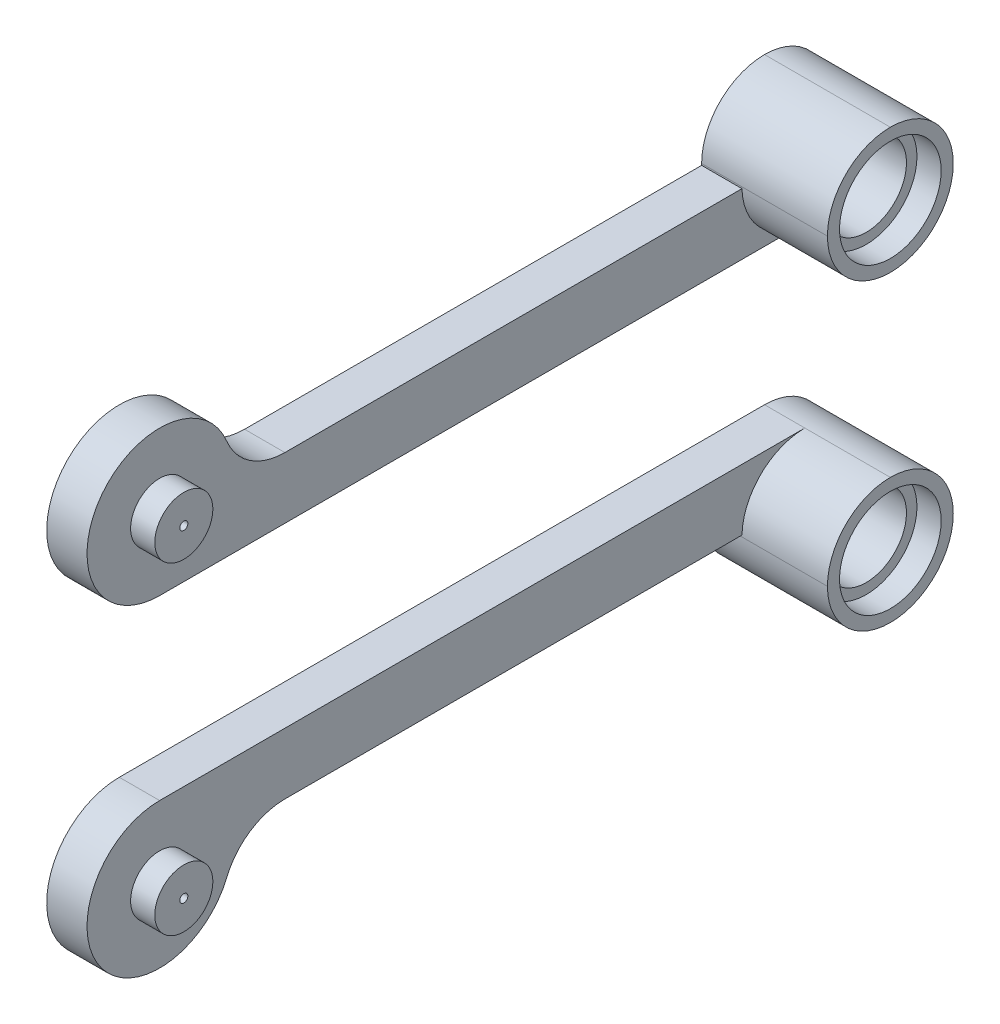
SolidWorks part; units mm, degrees
ref_plane "前视基准面" through (0, 0, 0) normal (0, 0, 1) x (1, 0, 0)
ref_plane "上视基准面" through (0, 0, 0) normal (0, 1, 0) x (1, 0, 0)
ref_plane "右视基准面" through (0, 0, 0) normal (1, 0, 0) x (0, 0, -1)
other "Configuration Table"
sketch "草图1" plane through (0, 0, 0) normal (1, 0, 0) x (0, 0, -1)
  line L0 (40, 3.3) -> (40, -4.5) construction
  line L1 (0, -4.5) -> (43.9, -4.5)
  line L2 (0, -4.5) -> (0, 3.3)
  line L3 (0, 3.3) -> (43.9, 3.3)
  line L4 (43.9, -4.5) -> (43.9, 3.3)
  line L6 (36.1, -4.5) -> (43.9, -4.5)
  line L7 (36.1, -4.5) -> (36.1, 3.3)
  line L8 (36.1, 3.3) -> (43.9, 3.3)
  line L9 (43.9, -4.5) -> (43.9, 3.3)
  line L10 (36.1, -4.5) -> (43.9, 3.3) construction
  line L11 (36.1, 3.3) -> (43.9, -4.5) construction
  circle A4 centre (0, 0) radius 1.8
  circle A5 centre (0, 0) radius 4.5
  circle A6 centre (40, -0.6) radius 2.5
  circle A7 centre (40, -0.6) radius 3.15
  circle A8 centre (0, 0) radius 0.25
  point P9 (40, -0.6)
  dimension "D1" = 3.6
  dimension "D4" = 40
  dimension "D5" = 3.9
  dimension "D2" = 9
  dimension "D6" = 5
  dimension "D7" = 6.3
  dimension "D8" = 0.5
  dimension "D3" = 7.8
extrude "凸台-拉伸1" add sketch "草图1" along normal blind 2.5 contours A5 | L3 L4 L1 L2
extrude "凸台-拉伸3" add sketch "草图1<6>" along normal blind 1.5 from surface contours L2 A4 | L2 A4 region at (0, 0, 0.7769) region at (0, 0, -0.7769) starting at face at (2.5, -0.0392, -21.2851)
sketch "草图1<6>" plane through (0, 0, 0) normal (1, 0, 0) x (0, 0, -1) same geometry as "草图1"
extrude "凸台-拉伸2" add sketch "草图1<5>" along normal blind 7.8 contours A6 | A7 A6 | L7 L1 L4 L3 A7 region at (0, -0.6, -36.2103) region at (0, -0.6, -40) region at (0, -0.6, -36.9391)
sketch "草图1<5>" plane through (0, 0, 0) normal (1, 0, 0) x (0, 0, -1) same geometry as "草图1"
extrude "切除-拉伸1" cut sketch "草图1<7>" along normal through all contours A6 region at (0, -0.6, -40)
sketch "草图1<7>" plane through (0, 0, 0) normal (1, 0, 0) x (0, 0, -1) same geometry as "草图1"
extrude "切除-拉伸2" cut sketch "草图1<8>" along normal blind 1.5 contours A7 A6 region at (0, -0.6, -36.9391)
sketch "草图1<8>" plane through (0, 0, 0) normal (1, 0, 0) x (0, 0, -1) same geometry as "草图1"
extrude "切除-拉伸3" cut sketch "草图1<9>" against normal blind 1.5 from surface contours A7 A6 region at (0, -0.6, -36.9391) starting at face at (7.8, -0.6, -42.5)
sketch "草图1<9>" plane through (0, 0, 0) normal (1, 0, 0) x (0, 0, -1) same geometry as "草图1"
sketch "草图2" plane through (0, 0, 0) normal (-1, 0, 0) x (0, 0, 1)
  line L0 (-3.0594, 3.3) -> (-43.9, 3.3) construction
  line L1 (-36.1, 3.3) -> (-4.5, 3.3)
  line L2 (-36.1, 3.3) -> (-36.1, -0.7)
  line L3 (-36.1, -0.7) -> (-4.5, -0.7)
  line L4 (-4.5, 3.3) -> (-4.5, -0.7)
  line L5 (-36.1, 3.3) -> (-36.1, -4.5) construction
  line L6 (-4.5, 3.3) -> (-3.0594, 3.3)
  arc A1 (0, -4.5) -> (-3.0594, 3.3) centre (0, 0) ccw construction
  circle A2 centre (0, 0) radius 4.5
  line M7 (-3.0594, 3.3) -> (-43.9, 3.3)
  dimension "D1" = 4
extrude "切除-拉伸4" cut sketch "草图2" against normal through all contours L4 L2 L3 M7 | A2 L4 M7 region at (0, 1.3, -20.3) region at (0, 2.5037, -4.083)
fillet "圆角1" radius 3.9 5 edges at (3.9, -4.5, -43.9) (3.9, 3.3, -43.9) (5.15, -4.5, -36.1) (3.9, 3.3, -36.1) (1.25, -0.7, -4.5)
ref_plane "基准面1" through (0, -10, 0) normal (0, 1, 0) x (1, 0, 0)
mirror "镜向2" about plane through (0, -10, 0) normal (0, 1, 0) of bodies 116 114
